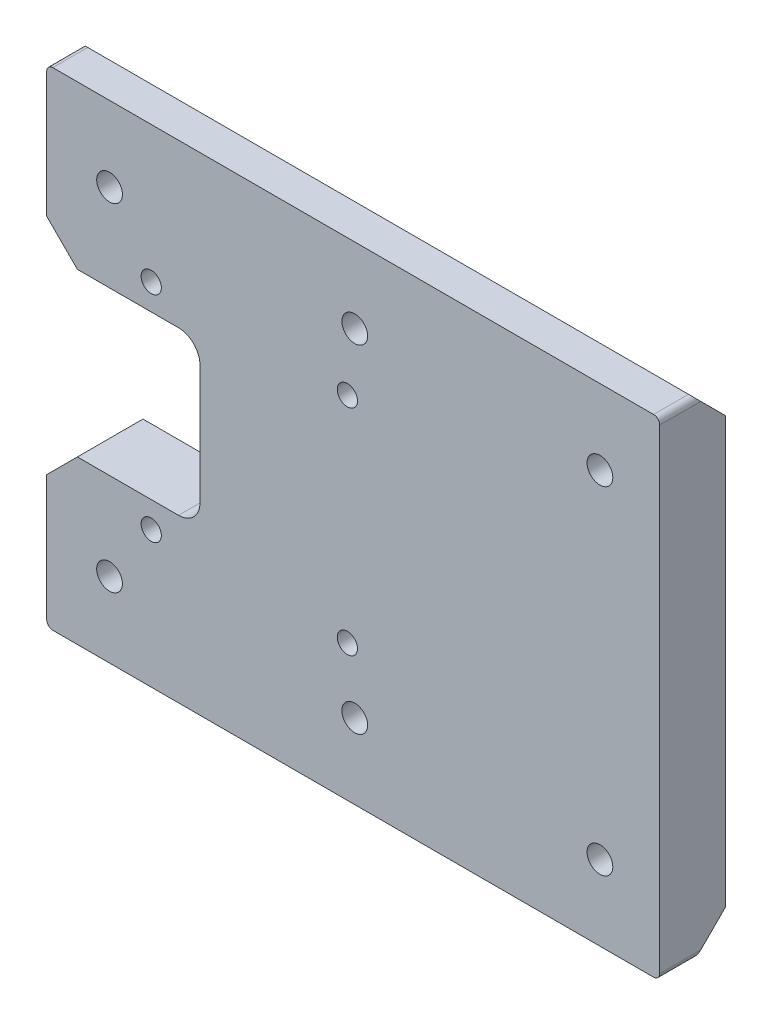
SolidWorks part; units mm, degrees
note: '?' marks a value the reader was unsure of.
ref_plane "Front Plane" through (0, 0, 0) normal (0, 0, 1) x (1, 0, 0)
ref_plane "Top Plane" through (0, 0, 0) normal (0, 1, 0) x (1, 0, 0)
ref_plane "Right Plane" through (0, 0, 0) normal (1, 0, 0) x (0, 0, -1)
ref_axis "Axis1" through (0, 0, -88.99) along (0, 0, 1)?
ref_axis "Axis2" through (0, -55, 0) along (0, 1, 0)?
ref_axis "Axis3" through (-88.99, 0, 0) along (1, 0, 0)?
sketch "Sketch1" plane through (0, 0, 0) normal (0, 0, 1) x (1, 0, 0)
  line L0 (0, 38.75) -> (0, 13.25)
  line L1 (0, 13.25) -> (25, 13.25)
  line L2 (25, 13.25) -> (25, -13.25)
  line L3 (1, 39.75) -> (99, 39.75)
  line L4 (100, 38.75) -> (100, -38.75)
  line L5 (0, 0) -> (25, 0) construction
  line L6 (1, -39.75) -> (99, -39.75)
  line L7 (0, -38.75) -> (0, -13.25)
  line L8 (0, -13.25) -> (25, -13.25)
  arc A0 (0, 38.75) -> (1, 39.75) centre (1, 38.75) cw
  arc A1 (1, -39.75) -> (0, -38.75) centre (1, -38.75) cw
  arc A2 (99, -39.75) -> (100, -38.75) centre (99, -38.75) ccw
  arc A3 (99, 39.75) -> (100, 38.75) centre (99, 38.75) cw
  point P13 (0, 39.75)
  point P16 (0, -39.75)
  point P19 (100, -39.75)
  point P22 (100, 39.75)
  dimension "D5" = 1
  dimension "D1" = 79.5
  dimension "D2" = 26.5
  dimension "D3" = 75
  dimension "D4" = 25
extrude "Boss-Extrude1" add sketch "Sketch1" along normal blind 12.7
chamfer "Chamfer1" distance 5 angle 45 2 edges at (0, 13.25, 6.35) (0, -13.25, 6.35)
fillet "Fillet1" radius 3.5 2 edges at (25, -13.25, 6.35) (25, 13.25, 6.35)
hole_wizard "CBORE for M6 Pan Head Machine Screw1" [suppressed] positions "Sketch3" profile "Sketch2" counterbore size "M6" standard "ANSI Metric"
sketch "Sketch3" plane through (0, 0, 12.7) normal (0, 0, 1) x (1, 0, 0)
  line L0 (10.25, 27.5) -> (90.25, 27.5) construction
  line L2 (0, 27.75) -> (0, 17.75) construction
  line L4 (0, 0) -> (100, 0) construction
  line L5 (100, -27.75) -> (100, 27.75) construction
  point P0 (10.25, 27.5)
  point P3 (90.25, 27.5)
  point P6 (10.25, -27.5)
  point P9 (90.25, -27.5)
  point P12 (50.25, -27.5)
  point P14 (50.25, 27.5)
  dimension "D1" = 10.25
  dimension "D2" = 40
  dimension "D3" = 55
sketch "Sketch2" plane through (10, 25, 12.7) normal (1, 0, 0) x (0, -1, 0)
  line L0 (0, 0) -> (0, 12.7)
  line L1 (0, 12.7) -> (3.3, 12.7)
  line L3 (3.3, 12.7) -> (3.3, 7.1)
  line L4 (3.3, 7.1) -> (6.5, 7.1)
  line L5 (6.5, 7.1) -> (6.5, 0)
  line L7 (6.5, 0) -> (0, 0)
  line L11 (0, -6.35) -> (0, 107.95) construction
  dimension "Thru Hole Dia." = 6.6
  dimension "Thru Hole Depth" = 12.7
  dimension "C'Bore Dia." = 13
  dimension "C'Bore Depth" = 7.1
hole_wizard "M5 Clearance Hole2" [suppressed] positions "Sketch5" profile "Sketch4" hole size "M5" standard "ANSI Metric"
sketch "Sketch5" plane through (0, 0, 12.7) normal (0, 0, 1) x (1, 0, 0)
  line L0 (35, 22.25) -> (35, -22.25) construction
  line L2 (0, 0) -> (35, 0) construction
  line L4 (25, -9.25) -> (25, 9.25) construction
  point P0 (35, 22.25)
  point P2 (35, -22.25)
  dimension "D1" = 10
  dimension "D2" = 44.5
sketch "Sketch4" plane through (35, 22.25, 12.7) normal (1, 0, 0) x (0, -1, 0)
  line L0 (0, 0) -> (0, 12.7)
  line L1 (0, 12.7) -> (2.75, 12.7)
  line L2 (2.75, 12.7) -> (2.75, 0)
  line L5 (2.75, 0) -> (0, 0)
  line L11 (0, -6.35) -> (0, 107.95) construction
  dimension "Thru Hole Dia." = 5.5
  dimension "Thru Hole Depth" = 12.7
hole_wizard "Tap Drill for M5x0.8 Tap1" positions "Sketch7" profile "Sketch6" hole size "M5x0.8" standard "ANSI Metric" end condition through all
sketch "Sketch7" plane through (0, 0, 12.7) normal (0, 0, 1) x (1, 0, 0)
  point P0 (10.25, 27.5)
  point P3 (50.25, 27.5)
  point P6 (90.25, 27.5)
  point P9 (90.25, -27.5)
  point P12 (50.25, -27.5)
  point P15 (10.25, -27.5)
sketch "Sketch6" plane through (10.25, 27.5, 12.7) normal (1, 0, 0) x (0, -1, 0)
  line L0 (0, 0) -> (0, 12.7)
  line L1 (0, 12.7) -> (2.1, 12.7)
  line L2 (2.1, 12.7) -> (2.1, 0)
  line L5 (2.1, 0) -> (0, 0)
  line L11 (0, -6.35) -> (0, 107.95) construction
  dimension "Thru Hole Dia." = 4.2
  dimension "Thru Hole Depth" = 12.7
sketch "Sketch8" plane through (0, 0, 0) normal (0, 0, -1) x (-1, 0, 0)
  line L0 (-62.5, 0) -> (-25, 0) construction
  line L1 (-84, -12.5) -> (-41, -12.5)
  line L2 (-87.5, -9) -> (-87.5, 9)
  line L3 (-84, 12.5) -> (-41, 12.5)
  line L4 (-37.5, -9) -> (-37.5, 9)
  line L5 (-87.5, -12.5) -> (-37.5, 12.5) construction
  line L6 (-87.5, 12.5) -> (-37.5, -12.5) construction
  line L7 (-62.5, 0) -> (-100, 0) construction
  line L10 (-21.5, 13.25) -> (-5, 13.25)
  line L11 (-5, 13.25) -> (0, 18.25)
  line L12 (0, 18.25) -> (0, 38.75)
  line L13 (-1, 39.75) -> (-99, 39.75)
  line L14 (-100, 38.75) -> (-100, -38.75)
  line L15 (-99, -39.75) -> (-1, -39.75)
  line L16 (0, -38.75) -> (0, -18.25)
  line L17 (0, -18.25) -> (-5, -13.25)
  line L18 (-5, -13.25) -> (-21.5, -13.25)
  line L19 (-25, -9.75) -> (-25, 9.75)
  line L20 (-21.5, 13.25) -> (-5, 13.25)
  line L21 (-5, 13.25) -> (0, 18.25)
  line L22 (0, 18.25) -> (0, 38.75)
  line L23 (-1, 39.75) -> (-99, 39.75)
  line L24 (-100, 38.75) -> (-100, -38.75)
  line L25 (-99, -39.75) -> (-1, -39.75)
  line L26 (0, -38.75) -> (0, -18.25)
  line L27 (0, -18.25) -> (-5, -13.25)
  line L28 (-5, -13.25) -> (-21.5, -13.25)
  line L29 (-25, -9.75) -> (-25, 9.75)
  arc A0 (-41, 12.5) -> (-37.5, 9) centre (-41, 9) cw
  arc A1 (-41, -12.5) -> (-37.5, -9) centre (-41, -9) ccw
  arc A2 (-84, -12.5) -> (-87.5, -9) centre (-84, -9) cw
  arc A3 (-87.5, 9) -> (-84, 12.5) centre (-84, 9) cw
  arc A6 (0, 38.75) -> (-1, 39.75) centre (-1, 38.75) ccw
  arc A7 (-99, 39.75) -> (-100, 38.75) centre (-99, 38.75) ccw
  arc A8 (-100, -38.75) -> (-99, -39.75) centre (-99, -38.75) ccw
  arc A9 (-1, -39.75) -> (0, -38.75) centre (-1, -38.75) ccw
  arc A10 (-25, -9.75) -> (-21.5, -13.25) centre (-21.5, -9.75) ccw
  arc A11 (-21.5, 13.25) -> (-25, 9.75) centre (-21.5, 9.75) ccw
  arc A12 (0, 38.75) -> (-1, 39.75) centre (-1, 38.75) ccw
  arc A13 (-99, 39.75) -> (-100, 38.75) centre (-99, 38.75) ccw
  arc A14 (-100, -38.75) -> (-99, -39.75) centre (-99, -38.75) ccw
  arc A15 (-1, -39.75) -> (0, -38.75) centre (-1, -38.75) ccw
  arc A16 (-25, -9.75) -> (-21.5, -13.25) centre (-21.5, -9.75) ccw
  arc A17 (-21.5, 13.25) -> (-25, 9.75) centre (-21.5, 9.75) ccw
  point P2 (-62.5, 0)
  dimension "D4" = 3.5
  dimension "D2" = 25
  dimension "D3" = 50
  dimension "D1" = 0
extrude "Cut-Extrude1" cut sketch "Sketch8" against normal blind 2
chamfer "Chamfer3" distance 5 angle 45 2 edges at (50, -39.75, 2) (50, 39.75, 2) tangent propagation no
hole_wizard "Tap Drill for M4x0.7 Tap1" positions "Sketch10" profile "Sketch9" hole size "M4x0.7" standard "ANSI Metric" end condition through all
sketch "Sketch10" plane through (0, 0, 12.7) normal (0, 0, 1) x (1, 0, 0)
  line L0 (0, 0) -> (38.1134, 0) construction
  line L4 (33.05, 0) -> (33.05, 32.4368) construction
  point P0 (17.05, 17.5)
  point P8 (17.05, -17.5)
  point P19 (49.05, -17.5)
  point P20 (49.05, 17.5)
  dimension "D1" = 17.05
  dimension "D2" = 35
  dimension "D3" = 32
sketch "Sketch9" plane through (17.05, 17.5, 12.7) normal (1, 0, 0) x (0, -1, 0)
  line L0 (0, 0) -> (0, 12.7)
  line L1 (0, 12.7) -> (1.65, 12.7)
  line L2 (1.65, 12.7) -> (1.65, 0)
  line L5 (1.65, 0) -> (0, 0)
  line L11 (0, -6.35) -> (0, 107.95) construction
  dimension "Thru Hole Dia." = 3.3
  dimension "Thru Hole Depth" = 12.7
fillet "Fillet2" [suppressed] radius 1.5
sketch "Sketch11" plane through (0, 0, 0) normal (0, 0, -1) x (-1, 0, 0)
  line L4 (-37.5, -9) -> (-37.5, 9)
  line L5 (-41, 12.5) -> (-84, 12.5)
  line L6 (-87.5, 9) -> (-87.5, -9)
  line L7 (-84, -12.5) -> (-41, -12.5)
  line L8 (-37.5, -9) -> (-37.5, 9)
  line L9 (-41, 12.5) -> (-84, 12.5)
  line L10 (-87.5, 9) -> (-87.5, -9)
  line L11 (-84, -12.5) -> (-41, -12.5)
  arc A4 (-37.5, 9) -> (-41, 12.5) centre (-41, 9) ccw
  arc A5 (-84, 12.5) -> (-87.5, 9) centre (-84, 9) ccw
  arc A6 (-87.5, -9) -> (-84, -12.5) centre (-84, -9) ccw
  arc A7 (-41, -12.5) -> (-37.5, -9) centre (-41, -9) ccw
  arc A8 (-37.5, 9) -> (-41, 12.5) centre (-41, 9) ccw
  arc A9 (-84, 12.5) -> (-87.5, 9) centre (-84, 9) ccw
  arc A10 (-87.5, -9) -> (-84, -12.5) centre (-84, -9) ccw
  arc A11 (-41, -12.5) -> (-37.5, -9) centre (-41, -9) ccw
  dimension "D1" = 0
extrude "Cut-Extrude2" cut sketch "Sketch11" against normal up to surface (2 mm away) up to face at (15.4, 17.5, 2)
